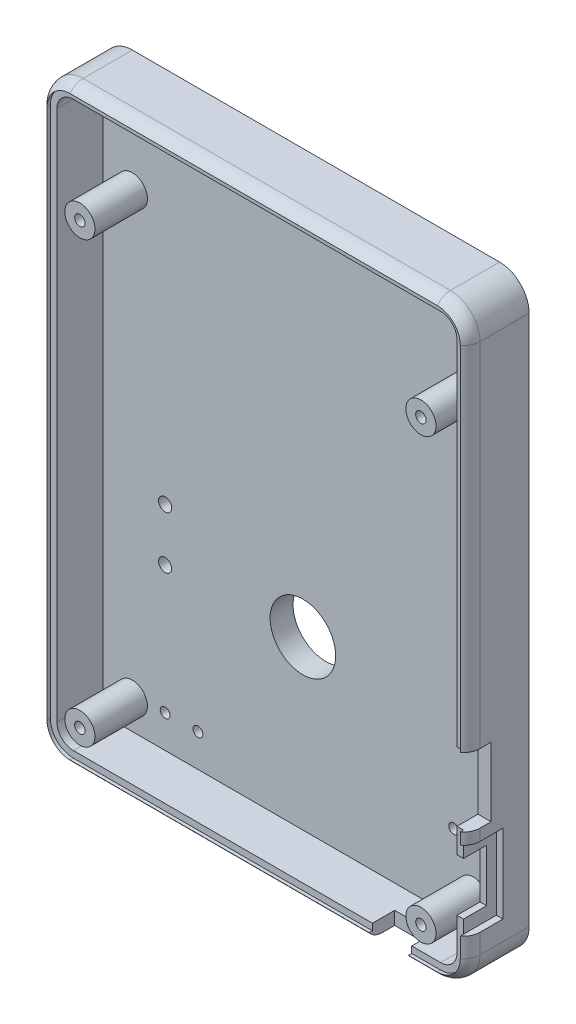
SolidWorks part; units mm, degrees
ref_plane "前基準面" through (0, 0, 0) normal (0, 0, 1) x (1, 0, 0)
ref_plane "上基準面" through (0, 0, 0) normal (0, 1, 0) x (1, 0, 0)
ref_plane "右基準面" through (0, 0, 0) normal (1, 0, 0) x (0, 0, -1)
sketch "草圖1" plane through (0, 0, 0) normal (0, 0, 1) x (1, 0, 0)
  line L0 (2, -2.5) -> (58, -2.5)
  line L1 (62.5, 2) -> (62.5, 83)
  line L2 (58, 87.5) -> (2, 87.5)
  line L3 (-2.5, 83) -> (-2.5, 2)
  arc A0 (58, -2.5) -> (62.5, 2) centre (58, 2) ccw
  arc A1 (62.5, 83) -> (58, 87.5) centre (58, 83) ccw
  arc A2 (2, 87.5) -> (-2.5, 83) centre (2, 83) ccw
  arc A3 (-2.5, 2) -> (2, -2.5) centre (2, 2) ccw
extrude "top plate" add sketch "草圖1" along normal blind 2
sketch "草圖2" plane through (0, 0, 0) normal (0, 0, 1) x (1, 0, 0)
  line L0 (2, -2.5) -> (58, -2.5)
  line L1 (62.5, 2) -> (62.5, 83)
  line L2 (58, 87.5) -> (2, 87.5)
  line L3 (-2.5, 83) -> (-2.5, 2)
  line L4 (2, -1.5) -> (58, -1.5)
  line L5 (61.5, 2) -> (61.5, 83)
  line L6 (58, 86.5) -> (2, 86.5)
  line L7 (-1.5, 83) -> (-1.5, 2)
  arc A0 (58, -2.5) -> (62.5, 2) centre (58, 2) ccw
  arc A1 (62.5, 83) -> (58, 87.5) centre (58, 83) ccw
  arc A2 (2, 87.5) -> (-2.5, 83) centre (2, 83) ccw
  arc A3 (-2.5, 2) -> (2, -2.5) centre (2, 2) ccw
  arc A4 (58, -1.5) -> (61.5, 2) centre (58, 2) ccw
  arc A5 (61.5, 83) -> (58, 86.5) centre (58, 83) ccw
  arc A6 (2, 86.5) -> (-1.5, 83) centre (2, 83) ccw
  arc A7 (-1.5, 2) -> (2, -1.5) centre (2, 2) ccw
extrude "wall outer half" add sketch "草圖2" along normal blind 10
sketch "草圖3" plane through (0, 0, 0) normal (0, 0, 1) x (1, 0, 0)
  line L0 (2, -1.5) -> (58, -1.5)
  line L1 (61.5, 2) -> (61.5, 83)
  line L2 (58, 86.5) -> (2, 86.5)
  line L3 (-1.5, 83) -> (-1.5, 2)
  line L4 (2, -0.5) -> (58, -0.5)
  line L5 (60.5, 2) -> (60.5, 83)
  line L6 (58, 85.5) -> (2, 85.5)
  line L7 (-0.5, 83) -> (-0.5, 2)
  arc A0 (58, -1.5) -> (61.5, 2) centre (58, 2) ccw
  arc A1 (61.5, 83) -> (58, 86.5) centre (58, 83) ccw
  arc A2 (2, 86.5) -> (-1.5, 83) centre (2, 83) ccw
  arc A3 (-1.5, 2) -> (2, -1.5) centre (2, 2) ccw
  arc A4 (58, -0.5) -> (60.5, 2) centre (58, 2) ccw
  arc A5 (60.5, 83) -> (58, 85.5) centre (58, 83) ccw
  arc A6 (2, 85.5) -> (-0.5, 83) centre (2, 83) ccw
  arc A7 (-0.5, 2) -> (2, -0.5) centre (2, 2) ccw
extrude "wall inner half" add sketch "草圖3" along normal blind 9
fillet "lens face round-over" radius 2.5 8 edges at (-1.182, -1.182, 10) (-2.5, 42.5, 10) (-1.182, 86.182, 10) (30, 87.5, 10) (61.182, 86.182, 10) (62.5, 42.5, 10) (61.182, -1.182, 10) (30, -2.5, 10)
sketch "草圖4" plane through (0, 0, 0) normal (0, 0, 1) x (1, 0, 0)
  circle A0 centre (30, 25) radius 8
  circle A1 centre (30, 25) radius 5
extrude "lens bezel ring" add sketch "草圖4" against normal blind 1.5
sketch "草圖5" plane through (0, 0, 0) normal (0, 0, 1) x (1, 0, 0)
  circle A0 centre (4, 4) radius 2.3
  circle A1 centre (56, 4) radius 2.3
  circle A2 centre (4, 71) radius 2.3
  circle A3 centre (56, 71) radius 2.3
extrude "corner posts" add sketch "草圖5" along normal blind 10
sketch "草圖6" plane through (0, 0, 0) normal (0, 0, 1) x (1, 0, 0)
  circle A0 centre (4, 4) radius 0.8
  circle A1 centre (56, 4) radius 0.8
  circle A2 centre (4, 71) radius 0.8
  circle A3 centre (56, 71) radius 0.8
extrude "post pilot holes M2" cut sketch "草圖6" against normal blind 7 from offset 10
sketch "草圖7" plane through (0, 0, 0) normal (0, 0, 1) x (1, 0, 0)
  line L0 (3.5, 49.5) -> (15.5, 49.5)
  line L1 (15.5, 49.5) -> (15.5, 50.5)
  line L2 (15.5, 50.5) -> (3.5, 50.5)
  line L3 (3.5, 50.5) -> (3.5, 49.5)
  line L4 (3.5, 53.5) -> (15.5, 53.5)
  line L5 (15.5, 53.5) -> (15.5, 54.5)
  line L6 (15.5, 54.5) -> (3.5, 54.5)
  line L7 (3.5, 54.5) -> (3.5, 53.5)
  line L8 (3.5, 57.5) -> (15.5, 57.5)
  line L9 (15.5, 57.5) -> (15.5, 58.5)
  line L10 (15.5, 58.5) -> (3.5, 58.5)
  line L11 (3.5, 58.5) -> (3.5, 57.5)
  line L12 (3.5, 61.5) -> (15.5, 61.5)
  line L13 (15.5, 61.5) -> (15.5, 62.5)
  line L14 (15.5, 62.5) -> (3.5, 62.5)
  line L15 (3.5, 62.5) -> (3.5, 61.5)
  line L16 (3.5, 65.5) -> (15.5, 65.5)
  line L17 (15.5, 65.5) -> (15.5, 66.5)
  line L18 (15.5, 66.5) -> (3.5, 66.5)
  line L19 (3.5, 66.5) -> (3.5, 65.5)
  line L20 (3.5, 69.5) -> (15.5, 69.5)
  line L21 (15.5, 69.5) -> (15.5, 70.5)
  line L22 (15.5, 70.5) -> (3.5, 70.5)
  line L23 (3.5, 70.5) -> (3.5, 69.5)
extrude "grip grooves" cut sketch "草圖7" along normal blind 0.6
sketch "草圖8" plane through (0, 0, 0) normal (0, 0, 1) x (1, 0, 0)
  circle A0 centre (9, 24) radius 1
  circle A1 centre (9, 32) radius 1
extrude "BOOT/RESET pinholes" cut sketch "草圖8" along normal through all
sketch "草圖9" plane through (0, 0, 0) normal (0, 1, 0) x (1, 0, 0)
  line L0 (47.6, -9.8) -> (53.6, -9.8)
  line L1 (53.6, -9.8) -> (53.6, -5.6)
  line L2 (53.6, -5.6) -> (47.6, -5.6)
  line L3 (47.6, -5.6) -> (47.6, -9.8)
extrude "shutter window" cut sketch "草圖9" against normal through all
sketch "草圖10" plane through (0, 0, 0) normal (0, 0, 1) x (1, 0, 0)
  circle A0 centre (30, 25) radius 5
extrude "lens hole" cut sketch "草圖10" along normal through all
sketch "草圖11" plane through (0, 0, 0) normal (0, 0, 1) x (1, 0, 0)
  circle A0 centre (14, 4.5) radius 0.75
  circle A1 centre (9, 4.5) radius 0.75
  circle A2 centre (53, 11.2) radius 0.75
extrude "LED light holes D1 D4 D5" cut sketch "草圖11" along normal through all
sketch "草圖12" plane through (0, 0, 0) normal (1, 0, 0) x (0, 0, -1)
  line L0 (-10, 18.75) -> (-5.8, 18.75)
  line L1 (-5.8, 18.75) -> (-5.8, 29.25)
  line L2 (-5.8, 29.25) -> (-10, 29.25)
  line L3 (-10, 29.25) -> (-10, 18.75)
extrude "USB-C window" cut sketch "草圖12" along normal blind 4.5 from offset 59
sketch "草圖13" plane through (0, 0, 0) normal (1, 0, 0) x (0, 0, -1)
  line L0 (-10, 7) -> (-5.5, 7)
  line L1 (-5.5, 7) -> (-5.5, 15)
  line L2 (-5.5, 15) -> (-10, 15)
  line L3 (-10, 15) -> (-10, 7)
extrude "power switch slot" cut sketch "草圖13" along normal blind 4.5 from offset 59
sketch "草圖14" plane through (0, 0, 0) normal (1, 0, 0) x (0, 0, -1)
  line L0 (-10, 5) -> (-4, 5)
  line L1 (-4, 5) -> (-4, 17)
  line L2 (-4, 17) -> (-10, 17)
  line L3 (-10, 17) -> (-10, 5)
extrude "switch finger pocket" cut sketch "草圖14" along normal blind 1.5 from offset 61.5
